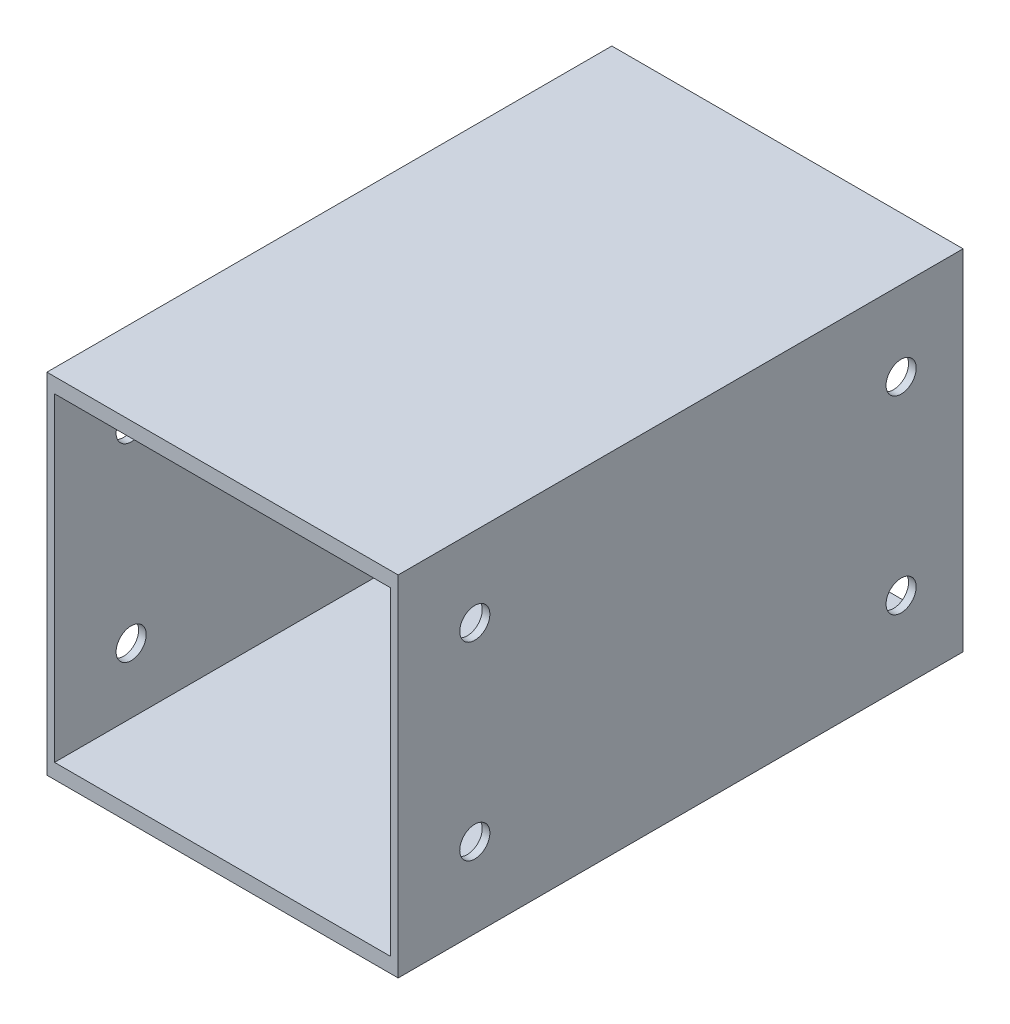
SolidWorks part; units mm, degrees
ref_plane "Alzado" through (0, 0, 0) normal (0, 0, 1) x (1, 0, 0)
ref_plane "Planta" through (0, 0, 0) normal (0, 1, 0) x (1, 0, 0)
ref_plane "Vista lateral" through (0, 0, 0) normal (1, 0, 0) x (0, 0, -1)
sketch "Croquis1" plane through (0, 0, 0) normal (0, 0, 1) x (1, 0, 0)
  line L5 (-22.5227, -21.3969) -> (22.5227, -21.3969)
  line L6 (-22.5227, -21.3969) -> (-22.5227, 21.3969)
  line L11 (-22.5227, 21.3969) -> (22.5227, 21.3969)
  line L12 (22.5227, -21.3969) -> (22.5227, 21.3969)
  line L17 (-22.5227, -21.3969) -> (22.5227, 21.3969) construction
  line L18 (-22.5227, 21.3969) -> (22.5227, -21.3969) construction
  line L19 (-22.3242, -21) -> (22.1258, -21)
  line L20 (-22.3242, -21) -> (-22.3242, 21)
  line L21 (-22.3242, 21) -> (22.1258, 21)
  line L22 (22.1258, -21) -> (22.1258, 21)
  line L23 (-23.5434, -23.3971) -> (23.5434, -23.3971)
  line L24 (-23.5434, -23.3971) -> (-23.5434, 23.3971)
  line L25 (-23.5434, 23.3971) -> (23.5434, 23.3971)
  line L26 (23.5434, -23.3971) -> (23.5434, 23.3971)
  line L27 (-23.5434, -23.3971) -> (23.5434, 23.3971) construction
  line L28 (-23.5434, 23.3971) -> (23.5434, -23.3971) construction
  point P0 (0, 0)
  point P6 (0, 0)
  dimension "D1" = 0.3969
  dimension "D2" = 0.3969
  dimension "D3" = 42
  dimension "D4" = 44.45
  dimension "D5" = 0.3969
  dimension "D6" = 0.1984
  dimension "D7" = 2.3971
  dimension "D8" = 1.0208
extrude "Saliente-Extruir1" add sketch "Croquis1" along normal blind 75.7317 contours L23 L26 L25 L24 L12 L5 L6 L11 region at (-22.8796, 0, 0)
sketch "Croquis2" plane through (-23.5434, 0, 0) normal (-1, 0, 0) x (0, 1, 0)
  line L0 (0, -75.7317) -> (0, -62.9794) construction
  line L1 (21, 0) -> (21, -7.4605) construction
  line L2 (23.794, -36.8817) -> (-13.0329, -36.8817) construction
  line L4 (-23.3971, -75.7317) -> (23.3971, -75.7317) construction
  circle A0 centre (12.7, -65.4567) radius 2.0193
  circle A1 centre (-12.7, -65.4567) radius 2.0193
  circle A2 centre (-12.7, -8.3067) radius 2.0193
  circle A3 centre (12.7, -8.3067) radius 2.0193
  point P4 (21, 0)
  point P5 (23.794, -36.83)
  point P17 (0, 0)
  point P23 (0, 0)
  dimension "D1" = 4.0386
  dimension "D4" = 57.15
  dimension "D2" = 10.275
  dimension "D3" = 8.3
extrude "Cortar-Extruir1" cut sketch "Croquis2" against normal through all
